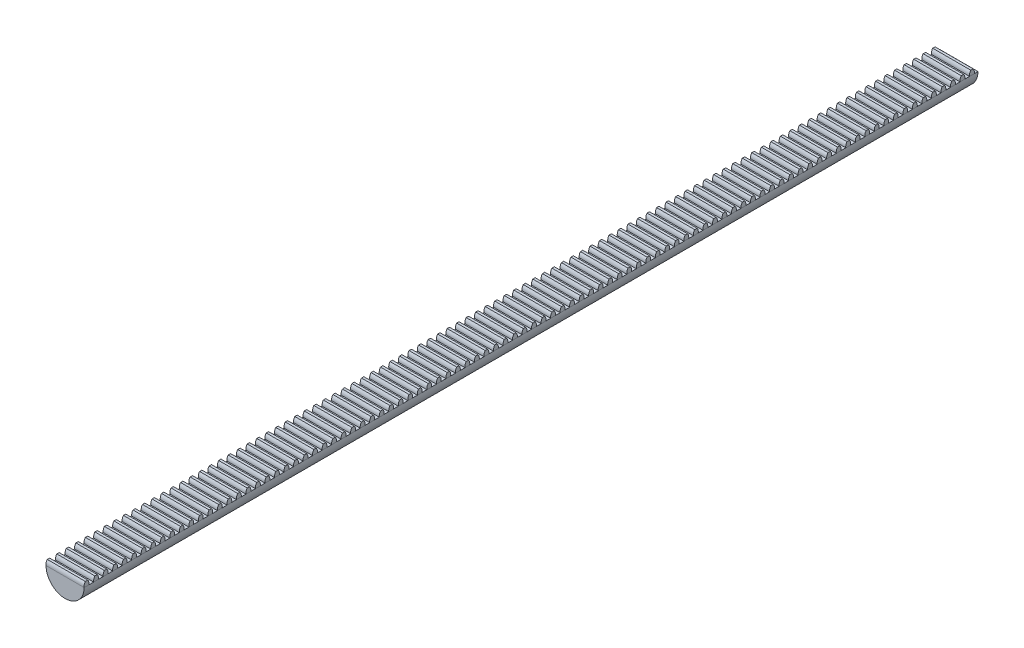
SolidWorks part; units mm, degrees
ref_plane "Front Plane" through (0, 0, 0) normal (0, 0, 1) x (1, 0, 0)
ref_plane "Top Plane" through (0, 0, 0) normal (0, 1, 0) x (1, 0, 0)
ref_plane "Right Plane" through (0, 0, 0) normal (1, 0, 0) x (0, 0, -1)
sketch "Sketch1" plane through (0, 0, 0) normal (0, 0, 1) x (1, 0, 0)
  line L0 (-20, 0) -> (20, 0)
  arc A0 (-20, 0) -> (20, 0) centre (0, 0) ccw
  dimension "D1" = 40
extrude "Boss-Extrude1" add sketch "Sketch1" along normal blind 825 and the other way blind 113.8576
sketch "Sketch2" plane through (0, 0, 0) normal (1, 0, 0) x (0, 0, -1)
  line L0 (-825, -20) -> (-825, 3.6676) construction
  line L1 (-825, 0) -> (-820, 0) construction
  line L2 (-825, 0) -> (113.8576, 0) construction
  line L3 (-822.5, 0) -> (-822.5, 5) construction
  line L4 (-822.5, 5) -> (-821.25, 5) construction
  line L5 (-822.5, 5) -> (-823.75, 5) construction
  line L6 (-823.75, 5) -> (-821.25, 5)
  line L7 (-825, 0) -> (-820, 0)
  spline S0 degree 2 poles (-825, 0) (-825.3769, 2.8504) (-823.75, 5) knots 0 0 0 1 1 1
  spline S1 degree 2 poles (-821.25, 5) (-819.6231, 2.8504) (-820, 0) knots 0 0 0 1 1 1
  dimension "D7" = 0.5
  dimension "D1" = 5
  dimension "D2" = 5
  dimension "D3" = 1.25
  dimension "D4" = 1.25
  dimension "D5" = 1.25
  dimension "D6" = 1.25
  dimension "D8" = 0.5
extrude "Boss-Extrude2" add sketch "Sketch2" along normal through all and the other way through all
pattern_linear "LPattern1" count 94 spacing 10 along (0, 0, 1) of "Boss-Extrude2"
